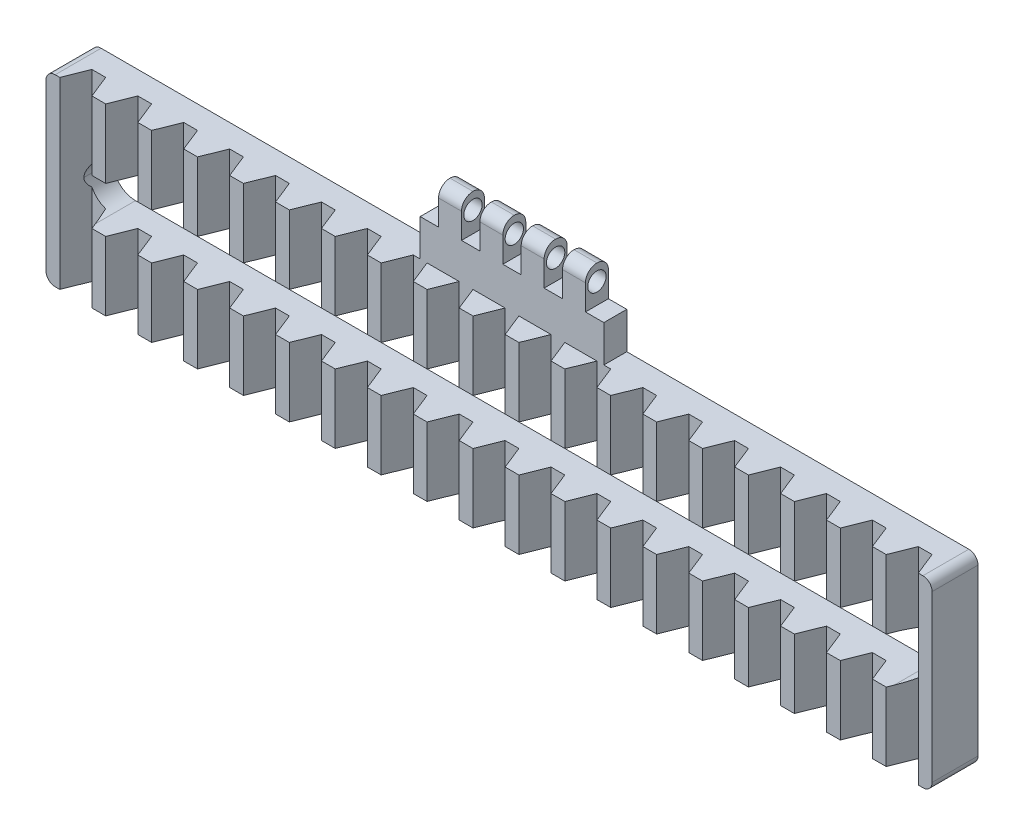
SolidWorks part; units mm, degrees
ref_plane "Front" through (0, 0, 0) normal (0, 0, 1) x (1, 0, 0)
ref_plane "Top" through (0, 0, 0) normal (0, 1, 0) x (1, 0, 0)
ref_plane "Right" through (0, 0, 0) normal (1, 0, 0) x (0, 0, -1)
sketch "Sketch1" plane through (0, 0, 0) normal (0, 1, 0) x (1, 0, 0)
  line L1 (96.5, -5) -> (-96.5, -5)
  line L2 (96.5, -5) -> (96.5, 5)
  line L3 (96.5, 5) -> (-96.5, 5)
  line L4 (-96.5, -5) -> (-96.5, 5)
  line L5 (96.5, -5) -> (-96.5, 5) construction
  line L6 (96.5, 5) -> (-96.5, -5) construction
  point P0 (0, 0)
  dimension "D1" = 10
  dimension "D2" = 193
extrude "Boss-Extrude1" add sketch "Sketch1" along normal blind 40
sketch "Sketch2" plane through (0, 0, 0) normal (0, 1, 0) x (1, 0, 0)
  line L0 (-96.5, -5) -> (-93.5, -5)
  line L1 (-96.5, -5) -> (96.5, -5) construction
  line L2 (-93.5, -5) -> (-91.5, 0)
  line L3 (-91.5, 0) -> (-88.5, 0)
  line L4 (-88.5, 0) -> (-86.5, -5)
  line L5 (-86.5, -5) -> (-83.5, -5)
  line L6 (-83.5, -5) -> (-81.5, 0)
  line L7 (-81.5, 0) -> (-78.5, 0)
  line L8 (-78.5, 0) -> (-76.5, -5)
  line L9 (-76.5, -5) -> (-73.5, -5)
  line L10 (-73.5, -5) -> (-71.5, 0)
  line L11 (-71.5, 0) -> (-68.5, 0)
  line L12 (-68.5, 0) -> (-66.5, -5)
  line L13 (-66.5, -5) -> (-63.5, -5)
  line L14 (-63.5, -5) -> (-61.5, 0)
  line L15 (-61.5, 0) -> (-58.5, 0)
  line L16 (-58.5, 0) -> (-56.5, -5)
  line L17 (-56.5, -5) -> (-53.5, -5)
  line L18 (-53.5, -5) -> (-51.5, 0)
  line L19 (-51.5, 0) -> (-48.5, 0)
  line L20 (-48.5, 0) -> (-46.5, -5)
  line L21 (-46.5, -5) -> (-43.5, -5)
  line L22 (-43.5, -5) -> (-41.5, 0)
  line L23 (-41.5, 0) -> (-38.5, 0)
  line L24 (-38.5, 0) -> (-36.5, -5)
  line L25 (-36.5, -5) -> (-33.5, -5)
  line L26 (-33.5, -5) -> (-31.5, 0)
  line L27 (-31.5, 0) -> (-28.5, 0)
  line L28 (-28.5, 0) -> (-26.5, -5)
  line L29 (-26.5, -5) -> (-23.5, -5)
  line L30 (-23.5, -5) -> (-21.5, 0)
  line L31 (-21.5, 0) -> (-18.5, 0)
  line L32 (-18.5, 0) -> (-16.5, -5)
  line L33 (-16.5, -5) -> (-13.5, -5)
  line L34 (-13.5, -5) -> (-11.5, 0)
  line L35 (-11.5, 0) -> (-8.5, 0)
  line L36 (-8.5, 0) -> (-6.5, -5)
  line L37 (-6.5, -5) -> (-3.5, -5)
  line L38 (-3.5, -5) -> (-1.5, 0)
  line L39 (-1.5, 0) -> (1.5, 0)
  line L40 (1.5, 0) -> (3.5, -5)
  line L41 (3.5, -5) -> (6.5, -5)
  line L42 (6.5, -5) -> (8.5, 0)
  line L43 (8.5, 0) -> (11.5, 0)
  line L44 (11.5, 0) -> (13.5, -5)
  line L45 (13.5, -5) -> (16.5, -5)
  line L46 (16.5, -5) -> (18.5, 0)
  line L47 (18.5, 0) -> (21.5, 0)
  line L48 (21.5, 0) -> (23.5, -5)
  line L49 (23.5, -5) -> (26.5, -5)
  line L50 (26.5, -5) -> (28.5, 0)
  line L51 (28.5, 0) -> (31.5, 0)
  line L52 (31.5, 0) -> (33.5, -5)
  line L53 (33.5, -5) -> (36.5, -5)
  line L54 (36.5, -5) -> (38.5, 0)
  line L55 (38.5, 0) -> (41.5, 0)
  line L56 (41.5, 0) -> (43.5, -5)
  line L57 (43.5, -5) -> (46.5, -5)
  line L58 (46.5, -5) -> (48.5, 0)
  line L59 (48.5, 0) -> (51.5, 0)
  line L60 (51.5, 0) -> (53.5, -5)
  line L61 (53.5, -5) -> (56.5, -5)
  line L62 (56.5, -5) -> (58.5, 0)
  line L63 (58.5, 0) -> (61.5, 0)
  line L64 (61.5, 0) -> (63.5, -5)
  line L65 (63.5, -5) -> (66.5, -5)
  line L66 (66.5, -5) -> (68.5, 0)
  line L67 (68.5, 0) -> (71.5, 0)
  line L68 (71.5, 0) -> (73.5, -5)
  line L69 (73.5, -5) -> (76.5, -5)
  line L70 (76.5, -5) -> (78.5, 0)
  line L71 (78.5, 0) -> (81.5, 0)
  line L72 (81.5, 0) -> (83.5, -5)
  line L73 (83.5, -5) -> (86.5, -5)
  line L74 (86.5, -5) -> (88.5, 0)
  line L75 (88.5, 0) -> (91.5, 0)
  line L76 (91.5, 0) -> (93.5, -5)
  line L77 (93.5, -5) -> (96.5, -5)
  line L81 (-96.5, -5) -> (-96.5, -20.768)
  line L82 (-96.5, -20.768) -> (96.5, -20.768)
  line L83 (96.5, -20.768) -> (96.5, -5)
  line L84 (101.5, 0) -> (103.5, -5) [skipped]
  line L85 (98.5, 0) -> (101.5, 0) [skipped]
  line L86 (96.5, -5) -> (98.5, 0) [skipped]
  dimension "D1" = 5
  dimension "D2" = 2
  dimension "D3" = 3
  dimension "D4" = 2
  dimension "D5" = 3
  dimension "D6" = 20
  dimension "D7" = 3
  dimension "D8" = 193
extrude "Cut-Extrude1" cut sketch "Sketch2" along normal blind 44 contours L82 L83 L77 L76 L75 L74 L73 L72 L71 L70 L69 L68 L67 L66 L65 L64 L63 L62 L61 L60 L59 L58 L57 L56 L55 L54 L53 L52 L51 L50 L49 L48 L47 L46 L45 L44 L43 L42 L41 L40 L39 L38 L37 L36 L35 L34 L33 L32 region at (0, 0, 11.5271)
sketch "Sketch3" plane through (0, 0, 0) normal (0, 0, 1) x (1, 0, 0)
  line L1 (92, 15) -> (-92, 15)
  line L2 (92, 15) -> (92, 25)
  line L3 (92, 25) -> (-92, 25)
  line L4 (-92, 15) -> (-92, 25)
  line L5 (92, 15) -> (-92, 25) construction
  line L6 (92, 25) -> (-92, 15) construction
  line L7 (91.5, 40) -> (88.5, 40) construction
  point P7 (90, 40)
  dimension "D1" = 92
  dimension "D2" = 10
  dimension "D3" = 15
  dimension "D4" = 92
  dimension "D5" = 15
extrude "Cut-Extrude2" cut sketch "Sketch3" against normal mid plane 44
fillet "Fillet1" radius 5 4 edges at (92, 15, -1.875) (92, 25, -1.875) (-92, 15, -1.875) (-92, 25, -1.875)
ref_plane "Plane1" through (0, 0, -5) normal (0, 0, 1) x (1, 0, 0)
sketch "Sketch4" plane through (0, 0, -5) normal (0, 0, 1) x (1, 0, 0)
  line L1 (-92, 30) -> (92, 30)
  line L2 (-92, 30) -> (-92, 35)
  line L3 (-92, 35) -> (92, 35)
  line L4 (92, 30) -> (92, 35)
  line L5 (-92, 30) -> (92, 35) construction
  line L6 (-92, 35) -> (92, 30) construction
  line L7 (-92, 10) -> (92, 10)
  line L8 (-92, 10) -> (-92, 5)
  line L9 (-92, 5) -> (92, 5)
  line L10 (92, 10) -> (92, 5)
  line L11 (-92, 10) -> (92, 5) construction
  line L12 (-92, 5) -> (92, 10) construction
  line L13 (-92, 28.5) -> (92, 28.5)
  line L14 (-92, 28.5) -> (-92, 36.5)
  line L15 (-92, 36.5) -> (92, 36.5)
  line L16 (92, 28.5) -> (92, 36.5)
  line L17 (-92, 28.5) -> (92, 36.5) construction
  line L18 (-92, 36.5) -> (92, 28.5) construction
  line L19 (-92, 3.5) -> (92, 3.5)
  line L20 (-92, 3.5) -> (-92, 11.5)
  line L21 (-92, 11.5) -> (92, 11.5)
  line L22 (92, 3.5) -> (92, 11.5)
  line L23 (-92, 3.5) -> (92, 11.5) construction
  line L24 (-92, 11.5) -> (92, 3.5) construction
  point P0 (0, 32.5)
  point P5 (0, 7.5)
  point P10 (0, 32.5)
  point P16 (0, 7.5)
  dimension "D1" = 184
  dimension "D2" = 184
  dimension "D3" = 5
  dimension "D4" = 5
  dimension "D5" = 7.5
  dimension "D6" = 32.5
  dimension "D7" = 8
  dimension "D8" = 4
  dimension "D9" = 8
  dimension "D10" = 4
extrude "Cut-Extrude3" cut sketch "Sketch4" along normal blind 4 contours L1 L4 L3 L2 | L10 L7 L8 L9 region at (0, 32.5, -5) region at (0, 7.5, -5)
fillet "Fillet3" radius 2 4 edges at (96.5, 0, 0) (96.5, 40, 0) (-96.5, 40, 0) (-96.5, 0, 0)
extrude "Cut-Extrude4" cut sketch "Sketch4<4>" along normal blind 2 contours L3 L16 L15 L14 | L13 L16 L1 L14 | L7 L22 L21 L20 | L19 L22 L9 L20 region at (0, 29.25, -5) region at (0, 35.75, -5) region at (0, 10.75, -5) region at (0, 4.25, -5)
sketch "Sketch4<4>" plane through (0, 0, -5) normal (0, 0, 1) x (1, 0, 0) same geometry as "Sketch4"
fillet "Fillet4" radius 2.5 8 edges at (92, 35, -2) (92, 30, -2) (-92, 35, -2) (-92, 30, -2) (-92, 10, -2) (-92, 5, -2) (92, 10, -2) (92, 5, -2)
fillet "Fillet5" radius 4 8 edges at (-92, 3.5, -4) (-92, 11.5, -4) (-92, 28.5, -4) (-92, 36.5, -4) (92, 11.5, -4) (92, 3.5, -4) (92, 28.5, -4) (92, 36.5, -4)
sketch "Sketch5" plane through (0, 40, 0) normal (0, 1, 0) x (1, 0, 0)
  line L1 (20, 0) -> (-20, 0)
  line L2 (20, 0) -> (20, 5)
  line L3 (20, 5) -> (-20, 5)
  line L4 (-20, 0) -> (-20, 5)
  line L5 (20, 0) -> (-20, 5) construction
  line L6 (20, 5) -> (-20, 0) construction
  point P0 (0, 2.5)
  dimension "D1" = 5
  dimension "D2" = 40
extrude "Boss-Extrude2" add sketch "Sketch5" along normal blind 8
sketch "Sketch6" plane through (0, 48, 0) normal (0, 1, 0) x (1, 0, 0)
  line L0 (20, 5) -> (-20, 5) construction
  line L1 (-16, 5) -> (-11, 5)
  line L2 (-16, 5) -> (-16, 0)
  line L3 (-16, 0) -> (-11, 0)
  line L4 (-11, 5) -> (-11, 0)
  line L5 (-13.5, 0) -> (-13.5, 5) construction
  line L6 (-16, 2.5) -> (-11, 2.5) construction
  line L7 (-20, 0) -> (20, 0) construction
  line L8 (-20, 5) -> (-20, 0) construction
  point P240 (-13.5, 2.5)
  dimension "D1" = 4
  dimension "D2" = 5
extrude "Boss-Extrude3" add sketch "Sketch6" along normal blind 8
fillet "Fillet6" radius 2.5 2 edges at (-13.5, 56, -5) (-13.5, 56, 0)
pattern_linear "LPattern1" count 4 spacing 9 along (1, 0, 0) of "Boss-Extrude3", "Fillet6"
sketch "Sketch7" plane through (-16, 0, 0) normal (-1, 0, 0) x (0, 0, 1)
  circle A0 centre (-2.5, 52.5) radius 2
  arc A1 (0, 53.5) -> (-2.5, 56) centre (-2.5, 53.5) ccw construction
  dimension "D1" = 1
extrude "Cut-Extrude5" cut sketch "Sketch7" against normal through all
